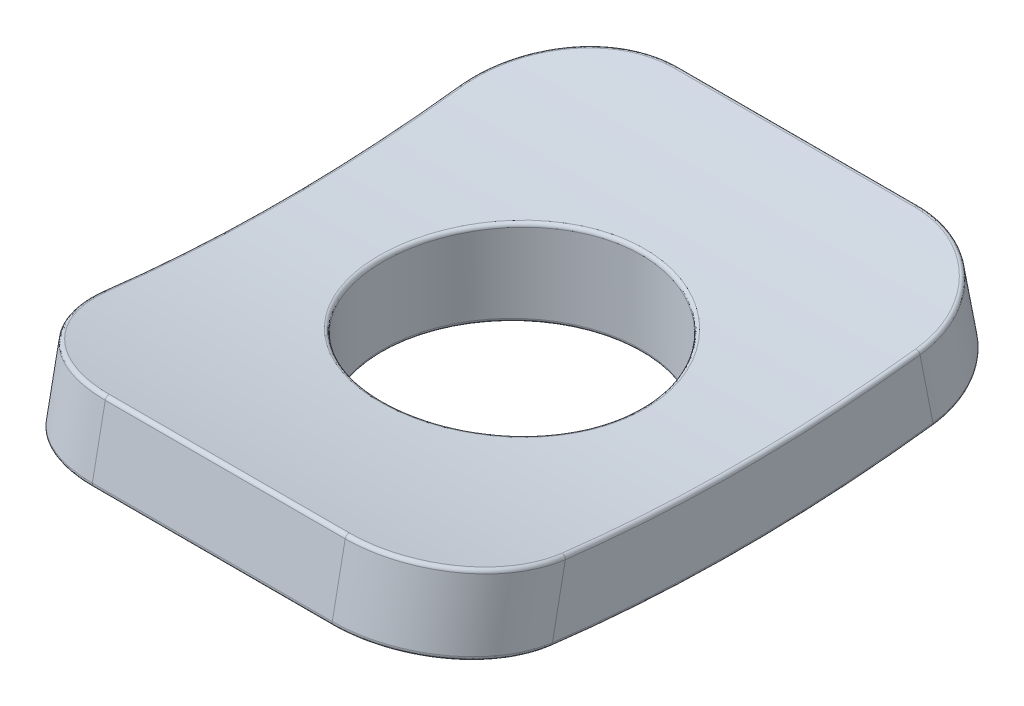
SolidWorks part; units mm, degrees
ref_plane "Front Plane" through (0, 0, 0) normal (0, 0, 1) x (1, 0, 0)
ref_plane "Top Plane" through (0, 0, 0) normal (0, 1, 0) x (1, 0, 0)
ref_plane "Right Plane" through (0, 0, 0) normal (1, 0, 0) x (0, 0, -1)
sketch "Sketch1" plane through (0, 0, 0) normal (1, 0, 0) x (0, 0, -1)
  line L0 (-7.75, 0.758) -> (-8.1375, -1.2041)
  line L1 (7.75, 0.758) -> (8.1375, -1.2041)
  arc A0 (-7.75, 0.758) -> (7.75, 0.758) centre (0, 40) ccw
  arc A1 (-8.1375, -1.2041) -> (8.1375, -1.2041) centre (0, 40) ccw
  point P3 (0, 0)
  dimension "D2" = 40
  dimension "D1" = 15.5
  dimension "D3" = 2
extrude "Boss-Extrude1" add sketch "Sketch1" along normal mid plane 12.5
fillet "Fillet1" radius 3 4 edges at (-6.25, -0.2231, 7.9438) (-6.25, -0.2231, -7.9438) (6.25, -0.2231, -7.9438) (6.25, -0.2231, 7.9438)
sketch "Sketch2" plane through (0, 0, 0) normal (0, 1, 0) x (1, 0, 0)
  circle A0 centre (0, 0) radius 3.5
  circle A1 centre (0, 0) radius 6
  dimension "D1" = 12
  dimension "D2" = 7
extrude "Cut-Extrude1" cut sketch "Sketch2" against normal through all both and the other way through all contours A0 region at (0, 0, 0)
extrude "Boss-Extrude2" add sketch "Sketch2<3>" along normal up to body from offset 2.25 separate body contours A1 | A0 offset against normal yes
sketch "Sketch2<3>" plane through (0, 0, 0) normal (0, 1, 0) x (1, 0, 0) same geometry as "Sketch2"
fillet "Fillet2" radius 0.1 19 edges at (0, -2.25, 3.5) (0.79, 0.1456, -3.4097) (-6.25, 0, 0) (-6.25, -2, 0) (6.25, 0, 0) (6.25, -2, 0) (0, 0.758, -7.75) (0, -1.2041, 8.1375) (0, 0.758, 7.75) (5.5943, -1.4078, 7.0279) (5.124, -1.3264, -7.4916) (-5.5943, -1.4078, -7.0279) (-5.124, -1.3264, 7.4916) (5.124, 0.6359, 7.1041) (5.5944, 0.555, -6.6401) (-5.124, 0.6359, -7.1041) (-5.5944, 0.555, 6.6401) (0, -2.25, 6) (0, -1.2041, -8.1375)
